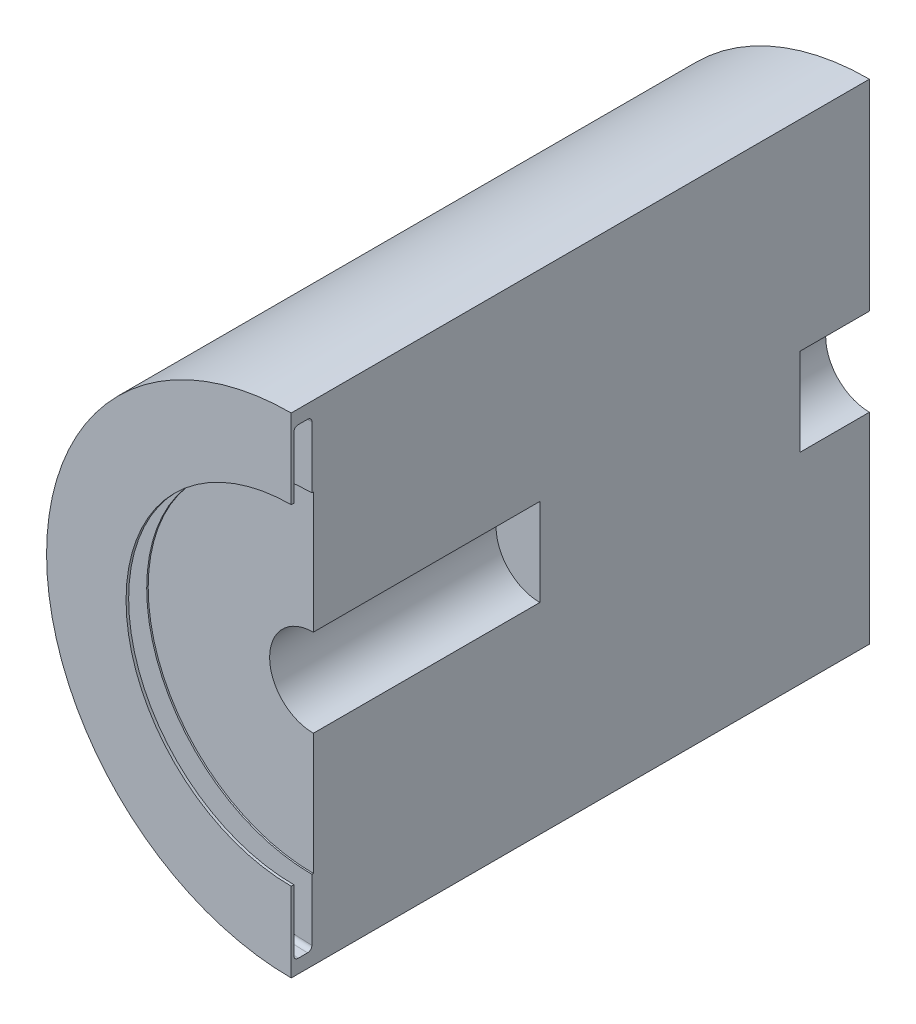
SolidWorks part; units mm, degrees
ref_plane "Front Plane" through (0, 0, 0) normal (0, 0, 1) x (1, 0, 0)
ref_plane "Top Plane" through (0, 0, 0) normal (0, 1, 0) x (1, 0, 0)
ref_plane "Right Plane" through (0, 0, 0) normal (1, 0, 0) x (0, 0, -1)
ref_plane "Plane3" through (13.6, 0, 0) normal (1, 0, 0) x (0, 0, -1)
sketch "Sketch4" plane through (13.6, 0, 0) normal (1, 0, 0) x (0, 0, -1)
  line L0 (-55.6887, -22.2003) -> (-55.6887, 16.9839) construction
  line L1 (-57.1887, 16.9839) -> (-57.1887, -22.2002) construction
  line L2 (-55.9887, 22.5) -> (-56.8887, 22.5) construction
  line L3 (-55.6887, -22.2003) -> (-55.6887, 16.1729)
  line L4 (-57.1887, 16.9839) -> (-57.1887, -22.2002)
  line L5 (-55.9887, 22.5) -> (-56.8887, 22.5)
  line L6 (-20, 0) -> (-61.396, 0) construction
  line L7 (-57.457, 16.1729) -> (-55.5434, 16.1729)
  line L8 (-57.457, 16.1729) -> (-57.457, 22.2)
  line L9 (-57.0161, 22.6183) -> (-56.1161, 22.6183)
  line L11 (-55.6887, 22.1922) -> (-55.6887, 16.1729)
  line L12 (-55.5434, 16.1729) -> (-55.5434, 4.2847)
  line L13 (-55.5434, 4.2847) -> (-33.3757, 4.2847)
  line L14 (-1.1042, 23.0717) -> (-1.1042, 4.2847)
  line L17 (-7.9108, 0) -> (-33.3757, 0)
  line L18 (-33.3757, 4.2847) -> (-33.3757, 0)
  line L19 (-57.457, 16.1729) -> (-57.7111, 16.1729)
  line L22 (-57.7111, 16.1729) -> (-57.7111, 23.0717)
  line L23 (-1.1042, 4.2847) -> (-7.9108, 4.2847)
  line L24 (-57.7111, 23.0717) -> (-57.7111, 23.9538)
  line L25 (-57.7111, 23.9538) -> (-1.1042, 23.9538)
  line L26 (-1.1042, 23.0717) -> (-1.1042, 23.9538)
  line L27 (-7.9108, 0) -> (-7.9108, 4.2847)
  arc A0 (-57.457, 22.2) -> (-57.0161, 22.6183) centre (-57.0285, 22.1898) cw
  arc A1 (-56.1161, 22.6183) -> (-55.6887, 22.1922) centre (-56.1148, 22.1922) cw
  point P14 (-5.6335, 0)
revolve "Revolve1" add sketch "Sketch4" angle 180 about L6 region at (13.6, 13.0512, 27.7498)
